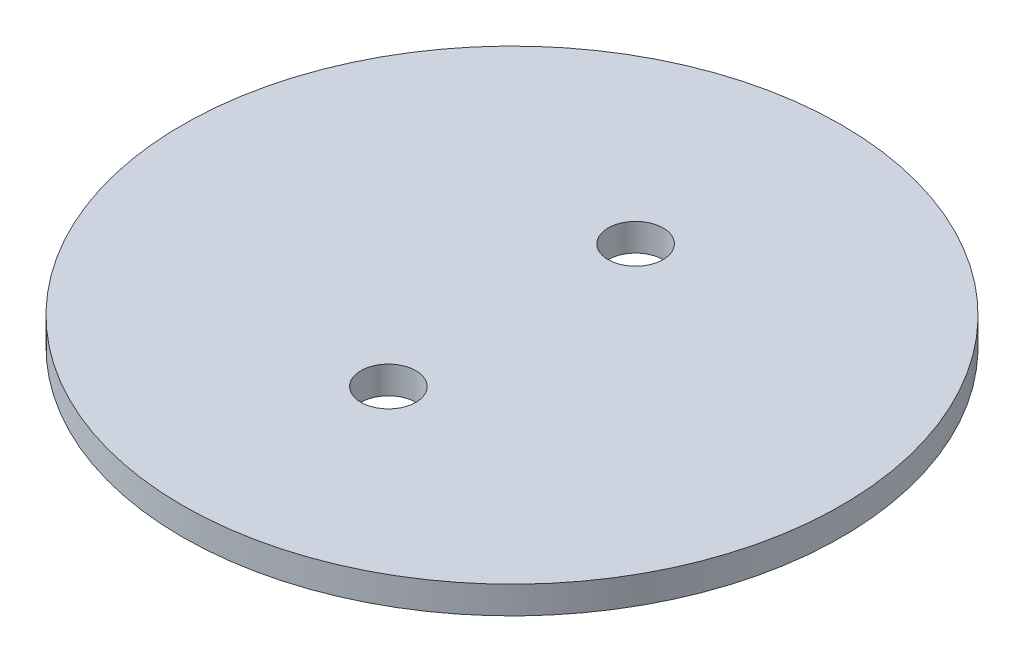
SolidWorks part; units mm, degrees
ref_plane "Front Plane" through (0, 0, 0) normal (0, 0, 1) x (1, 0, 0)
ref_plane "Top Plane" through (0, 0, 0) normal (0, 1, 0) x (1, 0, 0)
ref_plane "Right Plane" through (0, 0, 0) normal (1, 0, 0) x (0, 0, -1)
sketch "Sketch1" plane through (0, 0, 0) normal (0, 1, 0) x (1, 0, 0)
  line L0 (-28.5, 0) -> (28.5, 0) construction
  line L1 (0, 0) -> (0, 13.5)
  line L2 (0, 0) -> (0, -13.5)
  circle A0 centre (0, 0) radius 36
  circle A1 centre (28.5, 0) radius 3 construction
  circle A2 centre (-28.5, 0) radius 3 construction
  circle A3 centre (0, 13.5) radius 3
  circle A4 centre (0, -13.5) radius 3
  circle A5 centre (-28.5, 0) radius 6.25 construction
  circle A6 centre (0, 13.5) radius 12.5 construction
  circle A7 centre (0, -13.5) radius 12.5 construction
  circle A8 centre (28.5, 0) radius 6.25 construction
  point P2 (0, 0)
  point P11 (0, 0)
  point P17 (1.6819, 13.3948)
  dimension "D1" = 72
  dimension "D3" = 6
  dimension "D4" = 13.5
  dimension "D5" = 6
  dimension "D6" = 12.5
  dimension "D7" = 25
  dimension "D2" = 57
extrude "Boss-Extrude1" add sketch "Sketch1" against normal blind 3 contours A0 A4 A3 A2 A1 region at (-34.9818, 0, 0)
